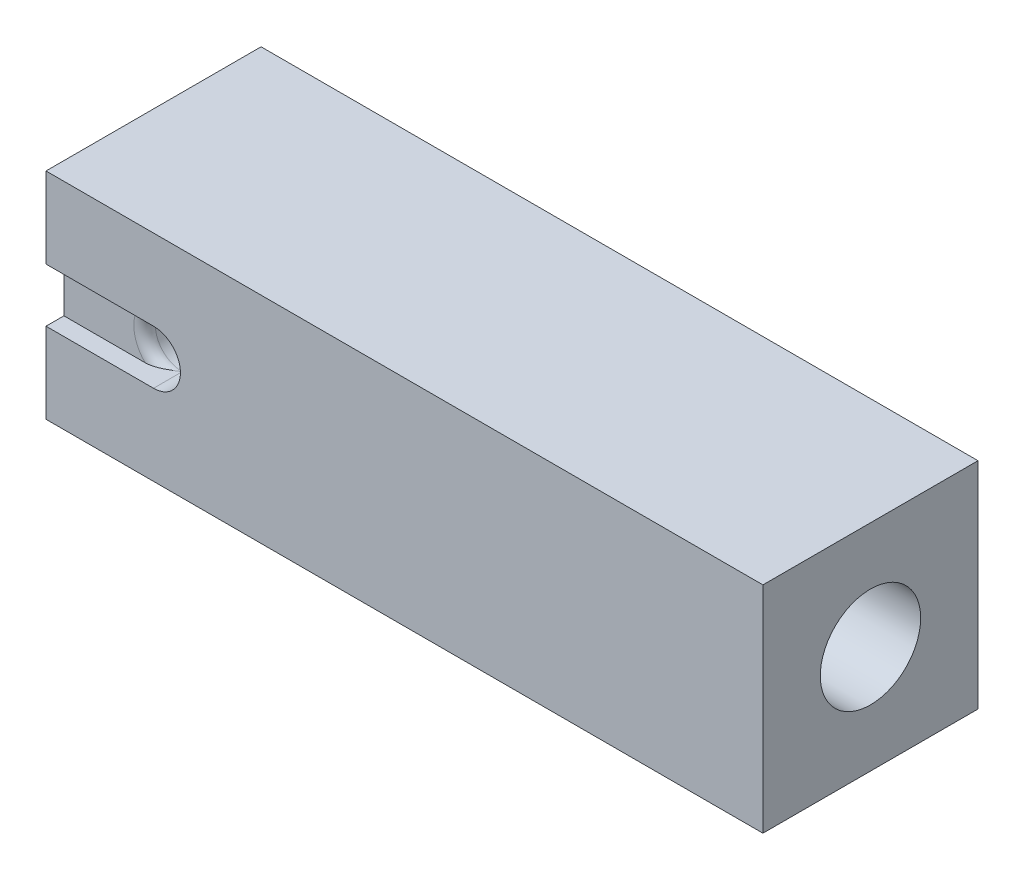
SolidWorks part; units mm, degrees
ref_plane "Front Plane" through (0, 0, 0) normal (0, 0, 1) x (1, 0, 0)
ref_plane "Top Plane" through (0, 0, 0) normal (0, 1, 0) x (1, 0, 0)
ref_plane "Right Plane" through (0, 0, 0) normal (1, 0, 0) x (0, 0, -1)
sketch "Sketch1" plane through (0, 0, 0) normal (0, 1, 0) x (1, 0, 0)
  line L1 (-10, 6) -> (10, 6)
  line L2 (-10, 6) -> (-10, 0)
  line L3 (-10, 0) -> (10, 0)
  line L4 (10, 6) -> (10, 0)
  point P4 (0, 0)
  dimension "D1" = 6
  dimension "D2" = 20
extrude "Boss-Extrude1" add sketch "Sketch1" along normal blind 6
sketch "Sketch2" plane through (10, 0, 0) normal (1, 0, 0) x (0, 0, -1)
  line L1 (0, 6) -> (6, 6) construction
  line L2 (6, 6) -> (6, 0) construction
  circle A0 centre (3, 3) radius 1.4
  point P2 (6, 3)
  point P6 (3, 6)
  dimension "D1" = 2.8
extrude "Cut-Extrude1" cut sketch "Sketch2" against normal blind 15
sketch "Sketch3" plane through (0, 0, -6) normal (0, 0, -1) x (-1, 0, 0)
  line L0 (10, 6) -> (10, 0) construction
  circle A0 centre (7, 3) radius 0.75
  point P4 (10, 3)
  dimension "D1" = 3
  dimension "D2" = 1.5
extrude "Cut-Extrude2" cut sketch "Sketch3" against normal up to surface (6 mm away) up to face at (0, 3, 0)
sketch "Sketch4" plane through (0, 0, -6) normal (0, 0, -1) x (-1, 0, 0)
  line L0 (7, 3.75) -> (10, 3.75)
  line L1 (10, 6) -> (10, 0) construction
  line L2 (10, 3.75) -> (10, 2.25)
  line L3 (10, 2.25) -> (7, 2.25)
  line L4 (7, 2.25) -> (7, 3.75)
  circle A0 centre (7, 3) radius 0.75 construction
extrude "Cut-Extrude3" cut sketch "Sketch4" against normal blind 0.5
ref_plane "Plane1" through (0, 0, -3) normal (0, 0, -1) x (-1, 0, 0)
mirror "Mirror1" about plane through (0, 0, -3) normal (0, 0, -1) of "Cut-Extrude3"
fillet "Fillet1" radius 0.3 2 edges at (-7.75, 3, -0.5) (-7.75, 3, -5.5)
